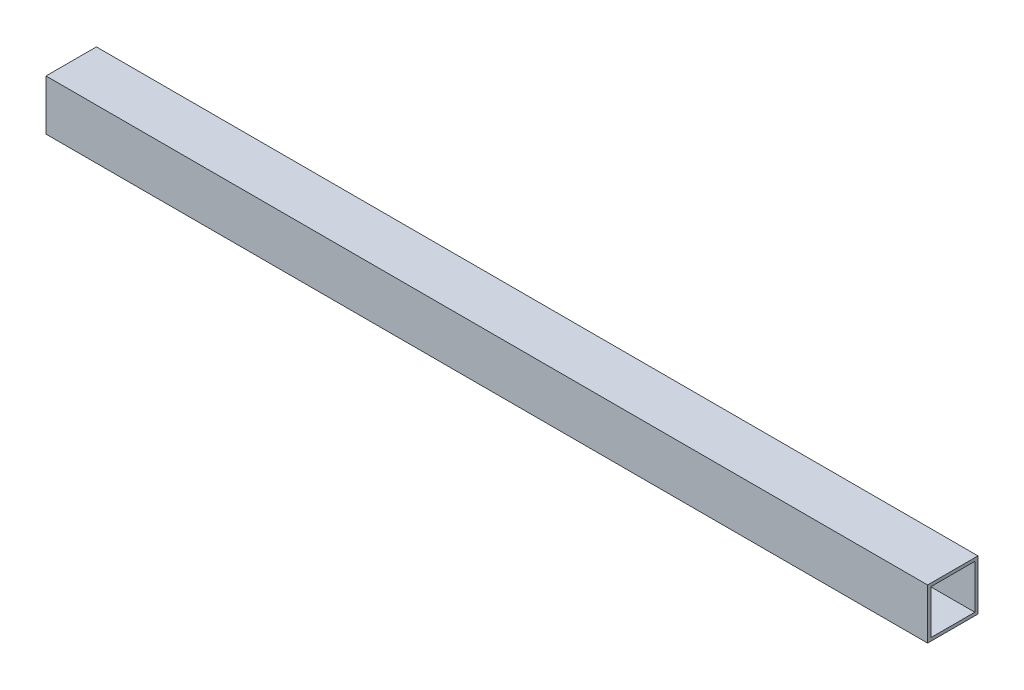
SolidWorks part; units mm, degrees
material "6061-T6 (SS)"
ref_plane "Front" through (0, 0, 0) normal (0, 0, 1) x (1, 0, 0)
ref_plane "Top" through (0, 0, 0) normal (0, 1, 0) x (1, 0, 0)
ref_plane "Right" through (0, 0, 0) normal (1, 0, 0) x (0, 0, -1)
sketch "Sketch1" plane through (0, 0, 0) normal (1, 0, 0) x (0, 0, -1)
  line L1 (-12.7, -12.7) -> (12.7, -12.7)
  line L2 (-12.7, -12.7) -> (-12.7, 12.7)
  line L3 (-12.7, 12.7) -> (12.7, 12.7)
  line L4 (12.7, -12.7) -> (12.7, 12.7)
  line L5 (-12.7, -12.7) -> (12.7, 12.7) construction
  line L6 (-12.7, 12.7) -> (12.7, -12.7) construction
  point P0 (0, 0)
  dimension "D1" = 25.4
extrude "Extrude-Thin1" add sketch "Sketch1" along normal up to surface (444.5 mm away) thin thin type one direction reverse wall 1.5875
